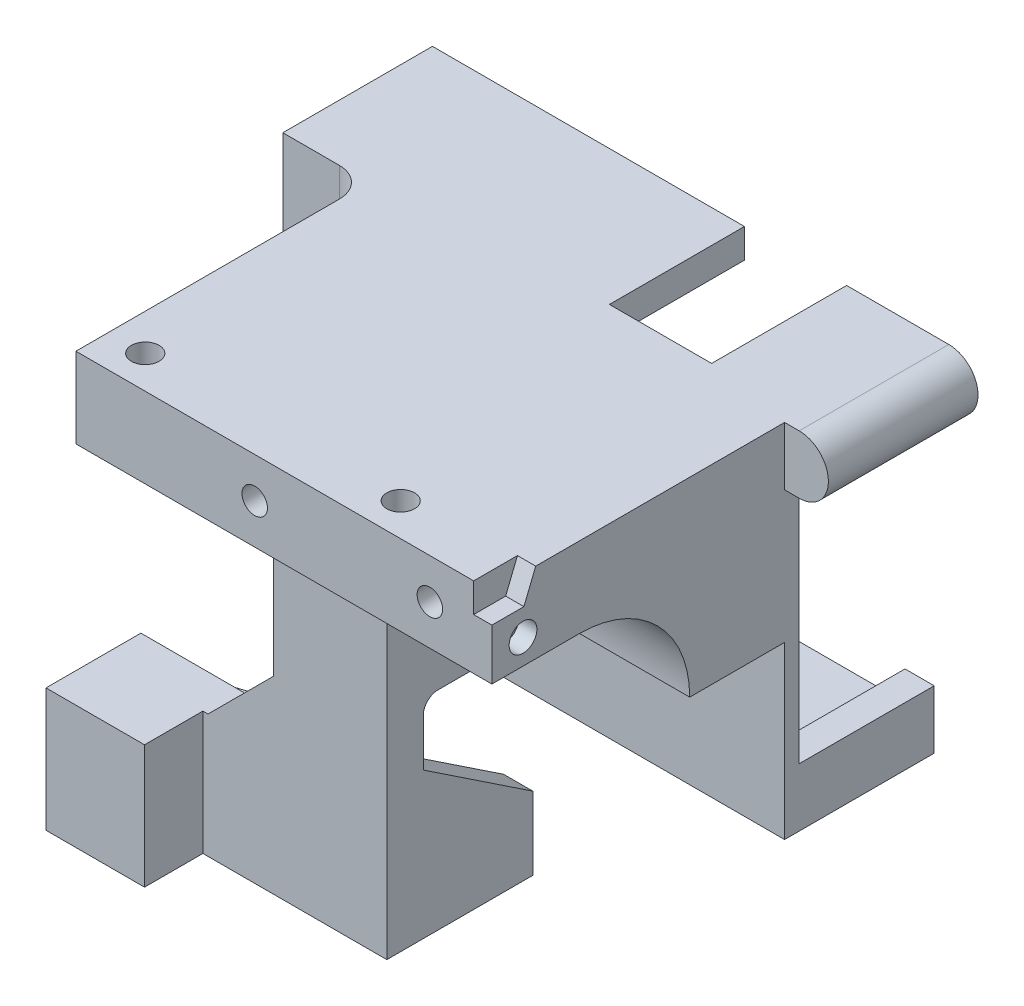
SolidWorks part; units mm, degrees
ref_plane "Plano frontal" through (0, 0, 0) normal (0, 0, 1) x (1, 0, 0)
ref_plane "Plano superior" through (0, 0, 0) normal (0, 1, 0) x (1, 0, 0)
ref_plane "Plano direito" through (0, 0, 0) normal (1, 0, 0) x (0, 0, -1)
sketch "Esboço2" plane through (0, 0, 0) normal (0, 0, 1) x (1, 0, 0)
  line L0 (0, 0) -> (0, -60.9)
  line L1 (0, -60.9) -> (-20, -60.9)
  line L2 (-20, -60.9) -> (-20, -25.9)
  line L3 (-20, -25.9) -> (-15.5, -15.9)
  line L4 (-15.5, -15.9) -> (-15.5, 0)
  line L5 (-15.5, 0) -> (0, 0)
  dimension "D1" = 15.5
  dimension "D2" = 60.9
  dimension "D3" = 35
  dimension "D4" = 15.9
  dimension "D5" = 20
extrude "Ressalto-extrusão1" add sketch "Esboço2" along normal blind 5
sketch "Esboço3" plane through (0, 0, 0) normal (1, 0, 0) x (0, 0, -1)
  line L0 (-5, 0) -> (0, 0)
  line L1 (6.1023, 6.1) -> (6.1023, 14.1) construction
  line L2 (6.1023, 6.1) -> (30.1023, 6.1)
  line L3 (6.1023, 14.1) -> (50.2046, 14.1)
  line L4 (45.2046, -9.0023) -> (45.2046, -60.9)
  line L5 (45.2046, -60.9) -> (50.2046, -60.9)
  line L6 (50.2046, -60.9) -> (50.2046, 14.1)
  arc A0 (6.1023, 6.1) -> (0, 0) centre (6.1023, -0.0023) ccw
  arc A1 (6.1023, 14.1) -> (-5, 0) centre (6.1018, 2.6794) ccw
  arc A2 (45.2046, -9.0029) -> (30.1016, 6.1) centre (30.1016, -9.0029) ccw
extrude "Ressalto-extrusão2" add sketch "Esboço3" against normal up to surface (15.5 mm away) up to face at (-15.5, -7.95, 2.5)
sketch "Esboço4" plane through (-15.5, 0, 0) normal (-1, 0, 0) x (0, 0, 1)
  line L0 (-50.2046, -60.9) -> (-50.2046, -40.9)
  line L2 (-50.2046, -40.9) -> (-65.2046, -50.9)
  line L3 (-65.2046, -50.9) -> (-65.2046, -60.9)
  line L4 (-65.2046, -60.9) -> (-65.2046, -50.9) construction
  line L5 (-65.2046, -60.9) -> (-50.2046, -40.9) construction
  line L6 (-65.2046, -60.9) -> (-50.2046, -60.9)
  line L13 (-50.2046, 14.1) -> (-50.2046, -60.9) construction
  dimension "D1" = 20
extrude "Ressalto-extrusão3" add sketch "Esboço4" against normal up to surface (15.5 mm away) up to face at (0, -18.647, -20.1425)
sketch "Esboço5" plane through (-20, 0, 0) normal (-1, 0, 0) x (0, 0, 1)
  line L0 (5, -60.9) -> (20, -60.9)
  line L1 (20, -60.9) -> (20, -50.9)
  line L2 (20, -50.9) -> (5, -40.9)
  line L3 (5, -25.9) -> (5, -60.9) construction
  line L4 (5, -40.9) -> (20, -50.9) construction
  line L5 (5, -40.9) -> (5, -60.9)
extrude "Ressalto-extrusão4" add sketch "Esboço5" against normal up to surface (20 mm away) up to face at (0, -22.8397, -27.0751)
sketch "Esboço6" plane through (-15.5, 0, 0) normal (-1, 0, 0) x (0, 0, 1)
  line L5 (-50.2046, -44.0023) -> (-45.2046, -44.0023)
  line L6 (-50.2046, -44.0023) -> (-50.2046, -60.9)
  line L7 (-50.2046, -60.9) -> (-45.2046, -60.9)
  line L8 (-45.2046, -44.0023) -> (-45.2046, -60.9)
extrude "Ressalto-extrusão5" add sketch "Esboço6" along normal blind 23.2
sketch "Esboço7" plane through (0, 0, -45.2046) normal (0, 0, 1) x (1, 0, 0)
  line L0 (-25.2, -44.0023) -> (-25.2, -60.9) construction
  line L1 (-38.7, -44.0023) -> (-25.2, -44.0023)
  line L2 (-38.7, -44.0023) -> (-38.7, -60.9)
  line L3 (-38.7, -60.9) -> (-25.2, -60.9)
  line L4 (-25.2, -44.0023) -> (-25.2, -60.9)
  line L5 (-38.7, -60.9) -> (0, -60.9) construction
extrude "Ressalto-extrusão6" add sketch "Esboço7" along normal blind 8
sketch "Esboço8" plane through (-15.5, 0, 0) normal (-1, 0, 0) x (0, 0, 1)
  line L1 (-45.2046, -9.0023) -> (-47.2046, -9.0023)
  line L2 (-45.2046, -9.0023) -> (-45.2046, -15.5904)
  line L3 (-45.2046, -15.5904) -> (-47.2046, -15.5904)
  line L4 (-47.2046, -9.0023) -> (-47.2046, -15.5904)
extrude "Corte-extrusão1" cut sketch "Esboço8" against normal through all
chamfer "Chanfro2" distance 9 angle 45 1 edges at (-15.5, -44.0023, -47.7046)
sketch "Esboço10" plane through (-15.5, 0, 0) normal (-1, 0, 0) x (0, 0, 1)
  line L0 (-50.2046, -40.9) -> (-50.2046, -60.9)
  line L1 (-50.2046, -60.9) -> (-65.2046, -60.9)
  line L2 (-65.2046, -60.9) -> (-65.2046, -50.9)
  line L3 (-65.2046, -50.9) -> (-50.2046, -40.9)
  dimension "D1" = 20
extrude "Ressalto-extrusão8" add sketch "Esboço10" along normal blind 4.5
sketch "Esboço9" plane through (0, -60.9, 0) normal (0, -1, 0) x (1, 0, 0)
  line L0 (-38.7, -50.2046) -> (-38.7, -53.2046)
  line L1 (-38.7, -53.2046) -> (-20, -59.2046)
  line L5 (-20, -65.2046) -> (-20, -50.2046) construction
  line L6 (-20, -59.2046) -> (-38.7, -53.2046) construction
  line L7 (-38.7, -50.2046) -> (-20, -50.2046)
  line L8 (-20, -50.2046) -> (-20, -59.2046)
extrude "Ressalto-extrusão7" add sketch "Esboço9" against normal blind 6 from offset 5.5 offset against normal yes
sketch "Esboço11" plane through (0, 0, 5) normal (0, 0, 1) x (1, 0, 0)
  line L0 (0, -40.9) -> (-20, -40.9) construction
  line L1 (-16, -40.9) -> (-4, -40.9)
  line L2 (-16, -40.9) -> (-16, -54.5408)
  line L3 (-16, -54.5408) -> (-4, -54.5408)
  line L4 (-4, -40.9) -> (-4, -54.5408)
  line L5 (-16, -50.9) -> (-16, -40.9) construction
extrude "Corte-extrusão2" cut sketch "Esboço11" along normal up to surface up to face at (-10, -45.9, 12.5)
sketch "Esboço13" plane through (0, -60.9, 0) normal (0, -1, 0) x (1, 0, 0)
  line L0 (0, 20) -> (-20, 20) construction
  line L1 (0, -65.2046) -> (-20, -65.2046) construction
  line L2 (0, -45.2046) -> (0, -65.2046) construction
  circle A0 centre (-10, 12.5) radius 1.6
  circle A1 centre (-9.7, -57.7046) radius 1.6
  point P5 (-10, 20)
  dimension "D1" = 3.2
  dimension "D3" = 3.2
  dimension "D2" = 7.5
  dimension "D4" = 9.7
  dimension "D5" = 7.5
extrude "Corte-extrusão4" cut sketch "Esboço13" against normal up to next
sketch "Esboço14" plane through (0, 0, 5) normal (0, 0, 1) x (1, 0, 0)
  line L0 (0, 0) -> (-15.5, 0) construction
  line L1 (-10.75, 0) -> (-4.75, 0)
  line L2 (-10.75, 0) -> (-10.75, -15.9)
  line L4 (-4.75, 0) -> (-4.75, -15.9)
  line L6 (-13, -40.9) -> (-7, -40.9)
  line L7 (-16, -54.5408) -> (-4, -54.5408) construction
  line L8 (0, -40.9) -> (-4, -40.9) construction
  line L9 (-10.75, -15.9) -> (-13, -25.9)
  line L10 (-13, -25.9) -> (-13, -40.9)
  line L11 (-7, -40.9) -> (-7, -25.9)
  line L12 (-7, -25.9) -> (-4.75, -15.9)
  point P6 (-7.75, 0)
  point P7 (-7.75, 0)
  point P11 (-10, -54.5408)
  point P14 (-10, -40.9)
  dimension "D1" = 6
  dimension "D2" = 6
extrude "Ressalto-extrusão9" add sketch "Esboço14" along normal blind 5
sketch "Esboço16" plane through (0, 0, -50.2046) normal (0, 0, -1) x (-1, 0, 0)
  line L0 (0, -40.9) -> (15.5, -40.9) construction
  line L1 (15.5009, -54.5427) -> (4, -54.5427)
  line L2 (15.5009, -54.5427) -> (15.5009, -40.9)
  line L3 (15.5009, -40.9) -> (4, -40.9)
  line L4 (4, -54.5427) -> (4, -40.9)
  line L5 (0, -50.9) -> (4, -40.9) construction
extrude "Corte-extrusão5" cut sketch "Esboço16" along normal through all
sketch "Esboço18" plane through (0, 0, 0) normal (1, 0, 0) x (0, 0, -1)
  line L5 (6.1023, 6.1) -> (30.1023, 6.1) construction
  line L6 (18.1023, 6.1) -> (50.2046, 6.1)
  line L7 (18.1023, 6.1) -> (18.1023, 17.1)
  line L8 (18.1023, 17.1) -> (50.2046, 17.1)
  line L9 (50.2046, 6.1) -> (50.2046, 17.1)
  line L10 (50.2046, -40.9) -> (50.2046, 14.1) construction
  line L11 (6.1023, 14.1) -> (50.2046, 14.1) construction
  dimension "D1" = 3
extrude "Ressalto-extrusão13" add sketch "Esboço18" along normal blind 62 and the other way up to surface
sketch "Esboço27" plane through (62, 0, 0) normal (1, 0, 0) x (0, 0, -1)
  line L1 (18.1023, 17.1) -> (50.2046, 17.1)
  line L2 (18.1023, 17.1) -> (18.1023, 6.1)
  line L3 (18.1023, 6.1) -> (50.2046, 6.1)
  line L4 (50.2046, 17.1) -> (50.2046, 6.1)
extrude "Corte-extrusão8" cut sketch "Esboço27" against normal blind 20.5
sketch "Esboço29" plane through (41.5, 0, 0) normal (1, 0, 0) x (0, 0, -1)
  line L0 (24.1023, 17.1) -> (22.4864, 13.1005)
  line L1 (50.2046, 17.1) -> (18.1023, 17.1) construction
  line L2 (22.4864, 13.1005) -> (18.1023, 13.1005)
  line L3 (18.1023, 17.1) -> (18.1023, 6.1) construction
  line L4 (18.1023, 13.1005) -> (18.1023, 17.1)
  line L5 (18.1023, 17.1) -> (24.1023, 17.1)
  line L7 (18.1023, 6.1) -> (50.2046, 6.1) construction
  circle A0 centre (22.3646, 9.5242) radius 1.9
  dimension "D4" = 3.8
  dimension "D1" = 6
  dimension "D2" = 3.9995
  dimension "D3" = 112
  dimension "D5" = 4.2623
  dimension "D6" = 3.4242
extrude "Corte-extrusão9" cut sketch "Esboço29" against normal blind 2.5
sketch "Esboço30" plane through (0, 17.1, 0) normal (0, 1, 0) x (1, 0, 0)
  circle A0 centre (-10.5, 22.6023) radius 1.9
  circle A1 centre (24.5, 22.6023) radius 1.9
  dimension "D1" = 3.8
extrude "Corte-extrusão10" cut sketch "Esboço30" against normal blind 6
sketch "Esboço32" plane through (0, 0, -18.1023) normal (0, 0, 1) x (1, 0, 0)
  line L0 (-15.5, 17.1) -> (39, 17.1) construction
  line L1 (-20, -60.9) -> (0, -60.9)
  line L2 (-20, -60.9) -> (-20, 17.1)
  line L3 (-20, 17.1) -> (0, 17.1)
  line L4 (0, -60.9) -> (0, 17.1)
extrude "Corte-extrusão11" cut sketch "Esboço32" along normal through all
sketch "Esboço33" plane through (0, 0, -18.1023) normal (0, 0, 1) x (1, 0, 0)
  circle A0 centre (9, 11.6) radius 1.75
  circle A1 centre (33, 11.6) radius 1.75
  dimension "D1" = 3.5
extrude "Corte-extrusão12" cut sketch "Esboço33" against normal blind 26
sketch "Esboço34" plane through (0, 0, -18.1023) normal (0, 0, 1) x (1, 0, 0)
  line L0 (9, 15.1796) -> (5.9, 13.3898)
  line L1 (5.9, 13.3898) -> (5.9, 9.8102)
  line L2 (5.9, 9.8102) -> (9, 8.0204) construction
  line L3 (9, 8.0204) -> (12.1, 9.8102) construction
  line L4 (12.1, 9.8102) -> (12.1, 13.3898)
  line L5 (12.1, 13.3898) -> (9, 15.1796)
  line L6 (5.9, 9.8102) -> (5.9, 6.1)
  line L7 (-15.5, 6.1) -> (41.5, 6.1) construction
  line L8 (5.9, 6.1) -> (12.1, 6.1)
  line L9 (12.1, 6.1) -> (12.1, 9.8102)
  line L10 (9, 11.6) -> (33, 11.6) construction
  line L11 (21, 11.6) -> (21, 6.1) construction
  line L12 (33, 8.0204) -> (29.9, 9.8102) construction
  line L13 (36.1, 9.8102) -> (33, 8.0204) construction
  line L14 (29.9, 6.1) -> (29.9, 9.8102)
  line L15 (36.1, 6.1) -> (29.9, 6.1)
  line L16 (36.1, 9.8102) -> (36.1, 6.1)
  line L17 (29.9, 13.3898) -> (33, 15.1796)
  line L18 (29.9, 9.8102) -> (29.9, 13.3898)
  line L19 (36.1, 13.3898) -> (36.1, 9.8102)
  line L20 (33, 15.1796) -> (36.1, 13.3898)
  circle A0 centre (9, 11.6) radius 3.5796 construction
  circle A1 centre (33, 11.6) radius 3.5796 construction
  dimension "D1" = 6.2
extrude "Corte-extrusão13" cut sketch "Esboço34" against normal blind 2.9 from offset 6 offset against normal yes
sketch "Esboço39" plane through (0, 0, -50.2046) normal (0, 0, -1) x (-1, 0, 0)
  line L0 (-41.5, 17.1) -> (-41.5, 6.1)
  line L5 (-41.5, 6.1) -> (0, 6.1)
  line L6 (0, 6.1) -> (0, -32.4)
  line L7 (0, -40.9) -> (0, 6.1) construction
  line L8 (0, -32.4) -> (15.5, -32.4)
  line L9 (15.5, 17.1) -> (15.5, -35.0023) construction
  line L10 (15.5, -32.4) -> (15.5, 17.1)
  line L11 (15.5, 17.1) -> (-41.5, 17.1)
  dimension "D1" = 49.5
extrude "Ressalto-extrusão20" add sketch "Esboço39" along normal blind 10
sketch "Esboço40" plane through (0, 0, -60.2046) normal (0, 0, -1) x (-1, 0, 0)
  line L0 (15.5, 17.1) -> (-41.5, 17.1) construction
  line L1 (-37.5, -28.4) -> (23.25, -28.4)
  line L2 (-37.5, -28.4) -> (-37.5, 13.1)
  line L3 (-37.5, 13.1) -> (23.25, 13.1)
  line L4 (23.25, -28.4) -> (23.25, 13.1)
  line L5 (-37.5, -28.4) -> (23.25, 13.1) construction
  line L6 (-37.5, 13.1) -> (23.25, -28.4) construction
  line L7 (-41.5, 17.1) -> (-41.5, 6.1) construction
  line L9 (27.25, -32.4) -> (-41.5, -32.4)
  line L10 (27.25, -32.4) -> (27.25, 17.1)
  line L11 (27.25, 17.1) -> (-41.5, 17.1)
  line L12 (-41.5, -32.4) -> (-41.5, 17.1)
  line L13 (27.25, -32.4) -> (-41.5, 17.1) construction
  line L14 (27.25, 17.1) -> (-41.5, -32.4) construction
  point P0 (-7.125, -7.65)
  point P10 (-7.125, -7.65)
  dimension "D1" = 60.75
  dimension "D2" = 41.5
  dimension "D3" = 4
  dimension "D4" = 4
extrude "Ressalto-extrusão21" add sketch "Esboço40" along normal blind 18.5
sketch "Esboço41" plane through (0, 0, -60.2046) normal (0, 0, 1) x (1, 0, 0)
  line L1 (-27.25, 17.1) -> (-15.5, 17.1)
  line L2 (-27.25, 17.1) -> (-27.25, -32.4)
  line L3 (-27.25, -32.4) -> (-15.5, -32.4)
  line L4 (-15.5, 17.1) -> (-15.5, -32.4)
  line L5 (0, 6.1) -> (41.5, 6.1)
  line L6 (0, 6.1) -> (0, -32.4)
  line L7 (0, -32.4) -> (41.5, -32.4)
  line L8 (41.5, 6.1) -> (41.5, -32.4)
extrude "Ressalto-extrusão22" add sketch "Esboço41" along normal blind 2
sketch "Esboço42" plane through (41.5, 0, 0) normal (1, 0, 0) x (0, 0, -1)
  line L0 (45.2046, -9.0023) -> (58.2046, -9.0023)
  line L1 (58.2046, -32.4) -> (58.2046, 6.1) construction
  line L2 (58.2046, -9.0023) -> (58.2046, 6.1)
  line L3 (58.2046, 6.1) -> (30.1016, 6.1)
  arc A0 (45.2046, -9.0023) -> (30.1016, 6.1) centre (30.1016, -9.0029) ccw
  arc A1 (45.2046, -9.0023) -> (30.1023, 6.1) centre (30.1016, -9.0029) ccw construction
extrude "Ressalto-extrusão23" add sketch "Esboço42" against normal blind 15.5
sketch "Esboço43" plane through (0, 0, -78.7046) normal (0, 0, -1) x (-1, 0, 0)
  line L0 (-41.5, 17.1) -> (-41.5, -32.4) construction
  line L1 (-41.5, 9.1) -> (-37.5, 9.1)
  line L2 (-41.5, 9.1) -> (-41.5, -24.4)
  line L3 (-41.5, -24.4) -> (-37.5, -24.4)
  line L4 (-37.5, 9.1) -> (-37.5, -24.4)
  line L5 (-37.5, 13.1) -> (-37.5, -28.4) construction
  line L6 (-7.125, 13.1) -> (-7.125, -28.4) construction
  line L7 (23.25, 13.1) -> (-37.5, 13.1) construction
  line L8 (-37.5, -28.4) -> (23.25, -28.4) construction
  line L9 (23.25, 13.1) -> (-37.5, 13.1) construction
  line L10 (-37.5, -28.4) -> (23.25, -28.4) construction
  line L11 (23.25, 9.1) -> (23.25, -24.4)
  line L12 (27.25, -24.4) -> (23.25, -24.4)
  line L13 (27.25, 9.1) -> (27.25, -24.4)
  line L14 (27.25, 9.1) -> (23.25, 9.1)
  line L15 (27.25, 17.1) -> (-41.5, 17.1) construction
  line L16 (-29.5, 17.1) -> (-15.5, 17.1)
  line L17 (-29.5, 17.1) -> (-29.5, 13.1)
  line L18 (-29.5, 13.1) -> (-15.5, 13.1)
  line L19 (-15.5, 17.1) -> (-15.5, 13.1)
  dimension "D1" = 4
  dimension "D2" = 4
  dimension "D3" = 8
  dimension "D4" = 14
extrude "Corte-extrusão14" cut sketch "Esboço43" against normal up to surface (18.5 mm away) up to face at (7.125, -7.65, -60.2046)
sketch "Esboço44" plane through (0, 0, -78.7046) normal (0, 0, -1) x (-1, 0, 0)
  line L0 (-29.5, 17.1) -> (-41.5, 17.1) construction
  line L1 (-37.5, 13.1) -> (-37.5, 9.1) construction
  line L2 (-43.5, 17.1) -> (-41.5, 17.1)
  line L3 (-41.5, 17.1) -> (-41.5, 9.1)
  line L4 (-41.5, 9.1) -> (-43.5, 9.1)
  line L5 (-41.5, -32.4) -> (27.25, -32.4) construction
  line L6 (23.25, -28.4) -> (23.25, -24.4) construction
  line L7 (29.25, -24.4) -> (27.25, -24.4)
  line L8 (27.25, -24.4) -> (27.25, -32.4)
  line L9 (27.25, -32.4) -> (29.25, -32.4)
  line L10 (27.25, -24.4) -> (23.25, -24.4) construction
  line L11 (27.25, 9.1) -> (27.25, -24.4) construction
  arc A0 (-43.5, 17.1) -> (-43.5, 9.1) centre (-43.5, 13.1) ccw
  arc A2 (29.25, -32.4) -> (29.25, -24.4) centre (29.25, -28.4) ccw
  dimension "D1" = 8
  dimension "D2" = 6
  dimension "D3" = 6
extrude "Ressalto-extrusão24" add sketch "Esboço44" against normal up to surface (20.5 mm away) up to face at (-21.375, -7.65, -58.2046)
sketch "Esboço45" plane through (0, 0, -78.7046) normal (0, 0, -1) x (-1, 0, 0)
  circle A0 centre (-43.5, 13.1) radius 1.8
  circle A1 centre (29.25, -28.4) radius 1.8
  dimension "D1" = 3.6
  dimension "D2" = 3.6
extrude "Corte-extrusão15" cut sketch "Esboço45" against normal blind 6
fillet "Filete1" radius 4 1 edges at (-15.5, -7.65, -58.2046)
fillet "Filete2" radius 2 1 edges at (-7.75, -32.4, -50.2046)
